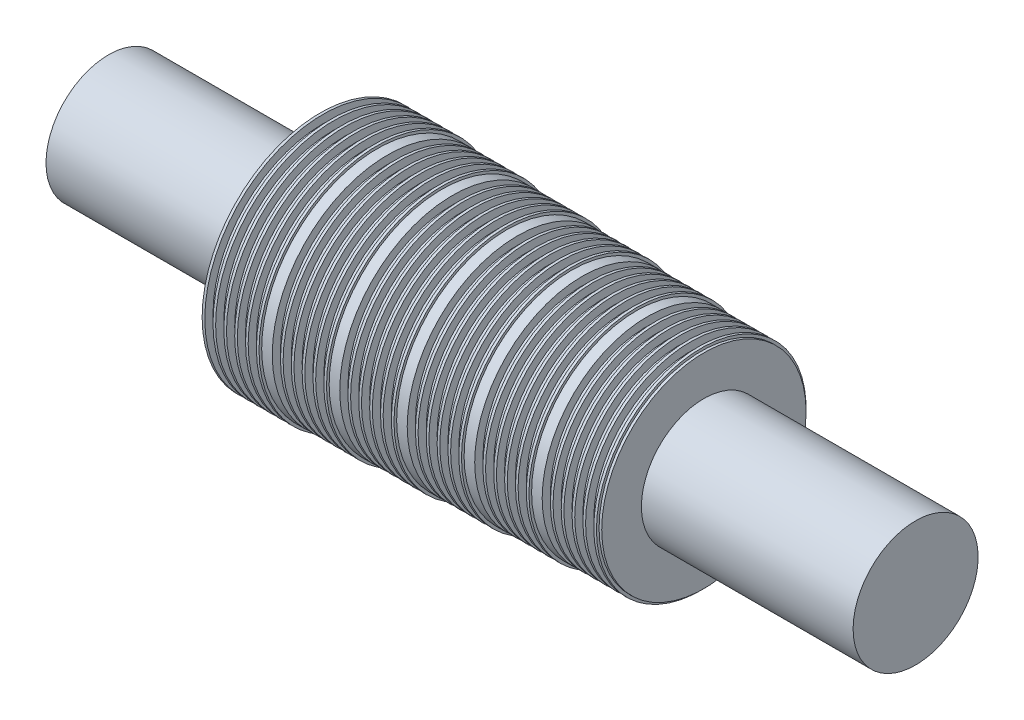
SolidWorks part; units mm, degrees
ref_plane "Front Plane" through (0, 0, 0) normal (0, 0, 1) x (1, 0, 0)
ref_plane "Top Plane" through (0, 0, 0) normal (0, 1, 0) x (1, 0, 0)
ref_plane "Right Plane" through (0, 0, 0) normal (1, 0, 0) x (0, 0, -1)
sketch "Sketch1" plane through (0, 0, 0) normal (0, 0, 1) x (1, 0, 0)
  line L24 (20.574, 11.334) -> (20.574, 10.5466)
  line L25 (20.574, 10.5466) -> (21.3614, 10.5466)
  line L26 (21.3614, 10.5466) -> (21.3614, 11.334)
  line L27 (21.3614, 11.334) -> (21.6154, 11.334)
  line L28 (21.6154, 11.334) -> (21.6154, 10.5466)
  line L29 (21.6154, 10.5466) -> (22.4028, 10.5466)
  line L30 (22.4028, 10.5466) -> (22.4028, 11.334)
  line L31 (22.4028, 11.334) -> (22.6568, 11.334)
  line L32 (22.6568, 11.334) -> (22.6568, 10.5466)
  line L33 (22.6568, 10.5466) -> (23.4442, 10.5466)
  line L34 (23.4442, 10.5466) -> (23.4442, 11.334)
  line L35 (23.4442, 11.334) -> (23.6982, 11.334)
  line L36 (23.6982, 11.334) -> (23.6982, 10.5466)
  line L37 (23.6982, 10.5466) -> (24.4856, 10.5466)
  line L38 (24.4856, 10.5466) -> (24.4856, 11.334)
  line L39 (24.4856, 11.334) -> (24.7396, 11.334)
  line L40 (24.7396, 11.334) -> (24.7396, 10.5466)
  line L41 (24.7396, 10.5466) -> (25.527, 10.5466)
  line L42 (25.527, 10.5466) -> (25.527, 11.334)
  line L43 (25.527, 11.334) -> (25.781, 11.334)
  line L44 (25.781, 11.334) -> (25.781, 11.08)
  line L45 (25.781, 11.08) -> (26.797, 11.08)
  line L46 (26.797, 11.08) -> (26.797, 10.2926)
  line L47 (26.797, 10.2926) -> (27.5844, 10.2926)
  line L48 (27.5844, 10.2926) -> (27.5844, 11.08)
  line L49 (27.5844, 11.08) -> (27.8384, 11.08)
  line L50 (27.8384, 11.08) -> (27.8384, 10.2926)
  line L51 (27.8384, 10.2926) -> (28.6258, 10.2926)
  line L52 (28.6258, 10.2926) -> (28.6258, 11.08)
  line L53 (28.6258, 11.08) -> (28.8798, 11.08)
  line L54 (28.8798, 11.08) -> (28.8798, 10.2926)
  line L55 (28.8798, 10.2926) -> (29.6672, 10.2926)
  line L56 (29.6672, 10.2926) -> (29.6672, 11.08)
  line L57 (29.6672, 11.08) -> (29.9212, 11.08)
  line L58 (29.9212, 11.08) -> (29.9212, 10.2926)
  line L59 (29.9212, 10.2926) -> (30.7086, 10.2926)
  line L60 (30.7086, 10.2926) -> (30.7086, 11.08)
  line L61 (30.7086, 11.08) -> (30.9626, 11.08)
  line L62 (30.9626, 11.08) -> (30.9626, 10.2926)
  line L63 (30.9626, 10.2926) -> (31.75, 10.2926)
  line L64 (31.75, 10.2926) -> (31.75, 11.08)
  line L65 (31.75, 11.08) -> (32.004, 11.08)
  line L66 (32.004, 11.08) -> (32.004, 10.826)
  line L67 (32.004, 10.826) -> (33.02, 10.826)
  line L68 (33.02, 10.826) -> (33.02, 10.0386)
  line L69 (33.02, 10.0386) -> (33.8074, 10.0386)
  line L70 (33.8074, 10.0386) -> (33.8074, 10.826)
  line L71 (33.8074, 10.826) -> (34.0614, 10.826)
  line L72 (34.0614, 10.826) -> (34.0614, 10.0386)
  line L73 (34.0614, 10.0386) -> (34.8488, 10.0386)
  line L74 (34.8488, 10.0386) -> (34.8488, 10.826)
  line L75 (34.8488, 10.826) -> (35.1028, 10.826)
  line L76 (35.1028, 10.826) -> (35.1028, 10.0386)
  line L77 (35.1028, 10.0386) -> (35.8902, 10.0386)
  line L78 (35.8902, 10.0386) -> (35.8902, 10.826)
  line L79 (35.8902, 10.826) -> (36.1442, 10.826)
  line L80 (36.1442, 10.826) -> (36.1442, 10.0386)
  line L81 (36.1442, 10.0386) -> (36.9316, 10.0386)
  line L82 (36.9316, 10.0386) -> (36.9316, 10.826)
  line L83 (36.9316, 10.826) -> (37.1856, 10.826)
  line L84 (37.1856, 10.826) -> (37.1856, 10.0386)
  line L85 (37.1856, 10.0386) -> (37.973, 10.0386)
  line L86 (37.973, 10.0386) -> (37.973, 10.826)
  line L87 (37.973, 10.826) -> (38.227, 10.826)
  line L88 (38.227, 10.826) -> (38.227, 10.572)
  line L89 (38.227, 10.572) -> (39.243, 10.572)
  line L90 (39.243, 10.572) -> (39.243, 9.7846)
  line L91 (39.243, 9.7846) -> (40.0304, 9.7846)
  line L92 (40.0304, 9.7846) -> (40.0304, 10.572)
  line L93 (40.0304, 10.572) -> (40.2844, 10.572)
  line L94 (40.2844, 10.572) -> (40.2844, 9.7846)
  line L95 (40.2844, 9.7846) -> (41.0718, 9.7846)
  line L96 (41.0718, 9.7846) -> (41.0718, 10.572)
  line L97 (41.0718, 10.572) -> (41.3258, 10.572)
  line L98 (41.3258, 10.572) -> (41.3258, 9.7846)
  line L99 (41.3258, 9.7846) -> (42.1132, 9.7846)
  line L100 (42.1132, 9.7846) -> (42.1132, 10.572)
  line L101 (42.1132, 10.572) -> (42.3672, 10.572)
  line L102 (42.3672, 10.572) -> (42.3672, 9.7846)
  line L103 (42.3672, 9.7846) -> (43.1546, 9.7846)
  line L104 (43.1546, 9.7846) -> (43.1546, 10.572)
  line L105 (43.1546, 10.572) -> (43.4086, 10.572)
  line L106 (43.4086, 10.572) -> (43.4086, 9.7846)
  line L107 (43.4086, 9.7846) -> (44.196, 9.7846)
  line L108 (44.196, 9.7846) -> (44.196, 10.572)
  line L109 (44.196, 10.572) -> (44.45, 10.572)
  line L110 (44.45, 10.572) -> (44.45, 10.318)
  line L111 (44.45, 10.318) -> (45.466, 10.318)
  line L112 (45.466, 10.318) -> (45.466, 9.5306)
  line L113 (45.466, 9.5306) -> (46.2534, 9.5306)
  line L114 (46.2534, 9.5306) -> (46.2534, 10.318)
  line L115 (46.2534, 10.318) -> (46.5074, 10.318)
  line L116 (46.5074, 10.318) -> (46.5074, 9.5306)
  line L117 (46.5074, 9.5306) -> (47.2948, 9.5306)
  line L118 (47.2948, 9.5306) -> (47.2948, 10.318)
  line L119 (47.2948, 10.318) -> (47.5488, 10.318)
  line L120 (47.5488, 10.318) -> (47.5488, 9.5306)
  line L121 (47.5488, 9.5306) -> (48.3362, 9.5306)
  line L122 (48.3362, 9.5306) -> (48.3362, 10.318)
  line L123 (48.3362, 10.318) -> (48.5902, 10.318)
  line L124 (48.5902, 10.318) -> (48.5902, 9.5306)
  line L125 (48.5902, 9.5306) -> (49.3776, 9.5306)
  line L126 (49.3776, 9.5306) -> (49.3776, 10.318)
  line L127 (49.3776, 10.318) -> (49.6316, 10.318)
  line L128 (49.6316, 10.318) -> (49.6316, 9.5306)
  line L129 (49.6316, 9.5306) -> (50.419, 9.5306)
  line L130 (50.419, 9.5306) -> (50.419, 10.318)
  line L131 (50.419, 10.318) -> (50.673, 10.318)
  line L132 (50.673, 10.318) -> (50.673, 10.064)
  line L133 (50.673, 10.064) -> (51.689, 10.064)
  line L134 (51.689, 10.064) -> (51.689, 9.2766)
  line L135 (51.689, 9.2766) -> (52.4764, 9.2766)
  line L136 (52.4764, 9.2766) -> (52.4764, 10.064)
  line L137 (52.4764, 10.064) -> (52.7304, 10.064)
  line L138 (52.7304, 10.064) -> (52.7304, 9.2766)
  line L139 (52.7304, 9.2766) -> (53.5178, 9.2766)
  line L140 (53.5178, 9.2766) -> (53.5178, 10.064)
  line L141 (53.5178, 10.064) -> (53.7718, 10.064)
  line L142 (53.7718, 10.064) -> (53.7718, 9.2766)
  line L143 (53.7718, 9.2766) -> (54.5592, 9.2766)
  line L144 (54.5592, 9.2766) -> (54.5592, 10.064)
  line L145 (54.5592, 10.064) -> (54.8132, 10.064)
  line L146 (54.8132, 10.064) -> (54.8132, 9.2766)
  line L147 (54.8132, 9.2766) -> (55.6006, 9.2766)
  line L148 (55.6006, 9.2766) -> (55.6006, 10.064)
  line L149 (55.6006, 10.064) -> (55.8546, 10.064)
  line L150 (55.8546, 10.064) -> (55.8546, 9.2766)
  line L151 (55.8546, 9.2766) -> (56.642, 9.2766)
  line L152 (56.642, 9.2766) -> (56.642, 10.064)
  line L153 (56.642, 10.064) -> (56.896, 10.064)
  line L154 (56.896, 10.064) -> (56.896, 9.81)
  line L155 (56.896, 9.81) -> (57.15, 9.81)
  line L156 (20.32, 6) -> (0, 6)
  line L157 (0, 6) -> (0, 0)
  line L158 (0, 0) -> (61.976, 0)
  line L159 (57.15, 6) -> (57.15, 9.81)
  line L160 (20.574, 11.334) -> (20.32, 11.334)
  line L161 (20.32, 11.334) -> (20.32, 6)
  line L162 (57.15, 6) -> (77.47, 6)
  line L163 (77.47, 6) -> (77.47, 0)
  line L164 (77.47, 0) -> (61.976, 0)
  point P5 (57.023, 9.81)
  point P6 (67.31, 6)
  dimension "D1" = 6
  dimension "D8" = 0.254
  dimension "D9" = 20.32
  dimension "D3" = 0.254
  dimension "D4" = 0.7874
  dimension "D5" = 0.7874
  dimension "D6" = 0.254
  dimension "D7" = 1.016
  dimension "D2" = 9.81
  dimension "D10" = 6
  dimension "D11" = 20.32
revolve "Revolve1" add sketch "Sketch1" angle 360 about L158
equation "\"kero_radius\"=0.23622in"
equation "\"D1@Sketch1\"=\"kero_radius\""
equation "\"lox_radius\"=0.23622in"
equation "\"Cavity_width\"=0.031in"
equation "\"tooth_width\"=0.01in"
equation "\"cavity_depth\"=0.031in"
equation "\"seal_step\"=0.01in"
equation "\"purge_length\"=0.04in"
equation "\"D3@Sketch1\"=\"tooth_width\""
equation "\"D4@Sketch1\"=\"Cavity_width\""
equation "\"D5@Sketch1\"=\"cavity_depth\""
equation "\"D6@Sketch1\"=\"seal_step\""
equation "\"D7@Sketch1\"=\"purge_length\""
equation "\"D2@Sketch1\"=\"lox_radius\"+.15"
equation "\"D10@Sketch1\"=\"lox_radius\""
